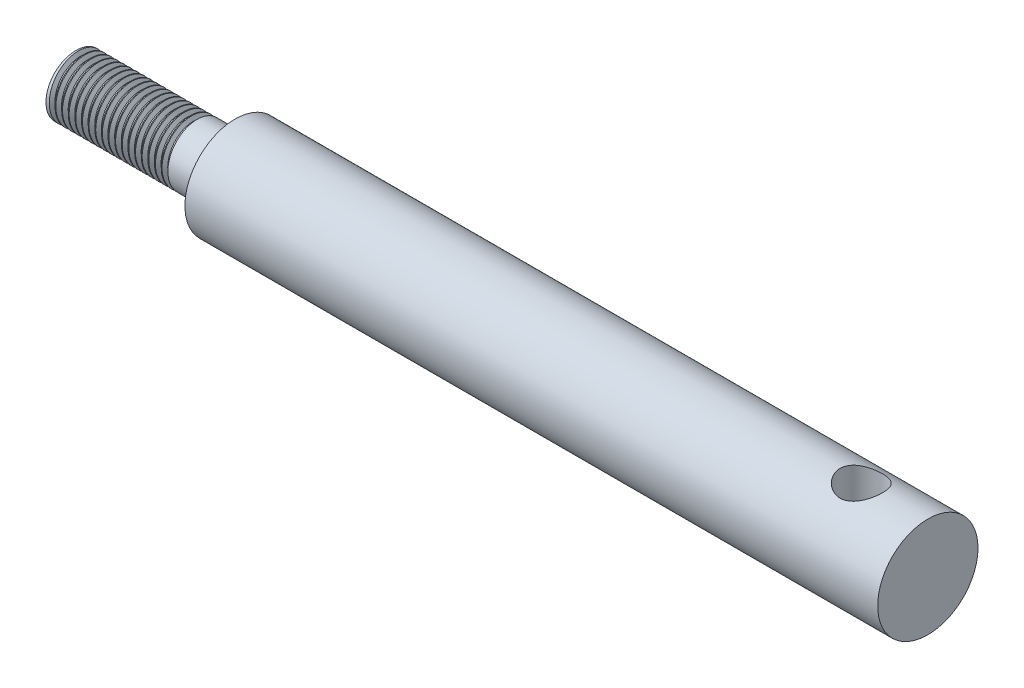
SolidWorks part; units mm, degrees
ref_plane "Front Plane" through (0, 0, 0) normal (0, 0, 1) x (1, 0, 0)
ref_plane "Top Plane" through (0, 0, 0) normal (0, 1, 0) x (1, 0, 0)
ref_plane "Right Plane" through (0, 0, 0) normal (1, 0, 0) x (0, 0, -1)
sketch "Sketch1" plane through (0, 0, 0) normal (1, 0, 0) x (0, 0, -1)
  circle A0 centre (0, 0) radius 8.001
  dimension "D1" = 16.002
extrude "Boss-Extrude1" add sketch "Sketch1" along normal blind 110.49
sketch "Sketch4" plane through (0, 0, 0) normal (-1, 0, 0) x (0, 0, 1)
  circle A0 centre (0, 0) radius 4.7625
  dimension "D1" = 9.525
extrude "Boss-Extrude2" add sketch "Sketch4" along normal blind 25.4
thread "Thread2" pitch 1.0583 method cut profile "Thread Profile2" start angle 0, offset 0, length 19.05, pitch 1.0583, diameter 9.525
ref_plane "Plane2" through (-25.4, 0, -4.7625) normal (0, -1, 0) x (0, 0, -1)
sketch "Thread Profile2" plane through (-25.4, 0, -4.7625) normal (0, -1, 0) x (0, 0, -1)
  line L0 (0, 0) -> (0, 1.0583) construction
  line L11 (0, 0) -> (0, 0.926)
  line L12 (0, 0.926) -> (-0.5728, 0.5953)
  line L13 (-0.5728, 0.5953) -> (-0.5728, 0.3307)
  line L15 (-0.5728, 0.3307) -> (0, 0)
  line L17 (-0.5728, 0.463) -> (0, 0.463) construction
  point P2 (0, 0)
  dimension "Pitch" = 1.0583
  dimension "Profile_Angle" = 60
  dimension "Profile_Land" = 0.2646
  dimension "Profile_Height" = 0.5728
ref_plane "Plane3" through (0, 8.001, 0) normal (0, 1, 0) x (1, 0, 0)
hole_wizard "1/4 Clearance Hole1" positions "Sketch22" profile "Sketch23" hole size "1/4" standard "ANSI Inch"
sketch "Sketch22" plane through (0, 8.001, 0) normal (0, 1, 0) x (1, 0, 0)
  point P0 (99.8779, 0)
  dimension "D1" = 99.8779
sketch "Sketch23" plane through (99.8779, 8.001, 0) normal (1, 0, 0) x (0, 0, 1)
  line L0 (0, 0) -> (0, 24.3818)
  line L1 (0, 24.3818) -> (3.3782, 22.352)
  line L2 (3.3782, 22.352) -> (3.3782, 0)
  line L5 (3.3782, 0) -> (0, 0)
  line L10 (0, 24.3818) -> (-3.3782, 22.352) construction
  line L11 (0, -6.35) -> (0, 107.95) construction
  dimension "Hole Dia." = 6.7564
  dimension "Hole Depth" = 22.352
  dimension "Drill Angle" = 118
